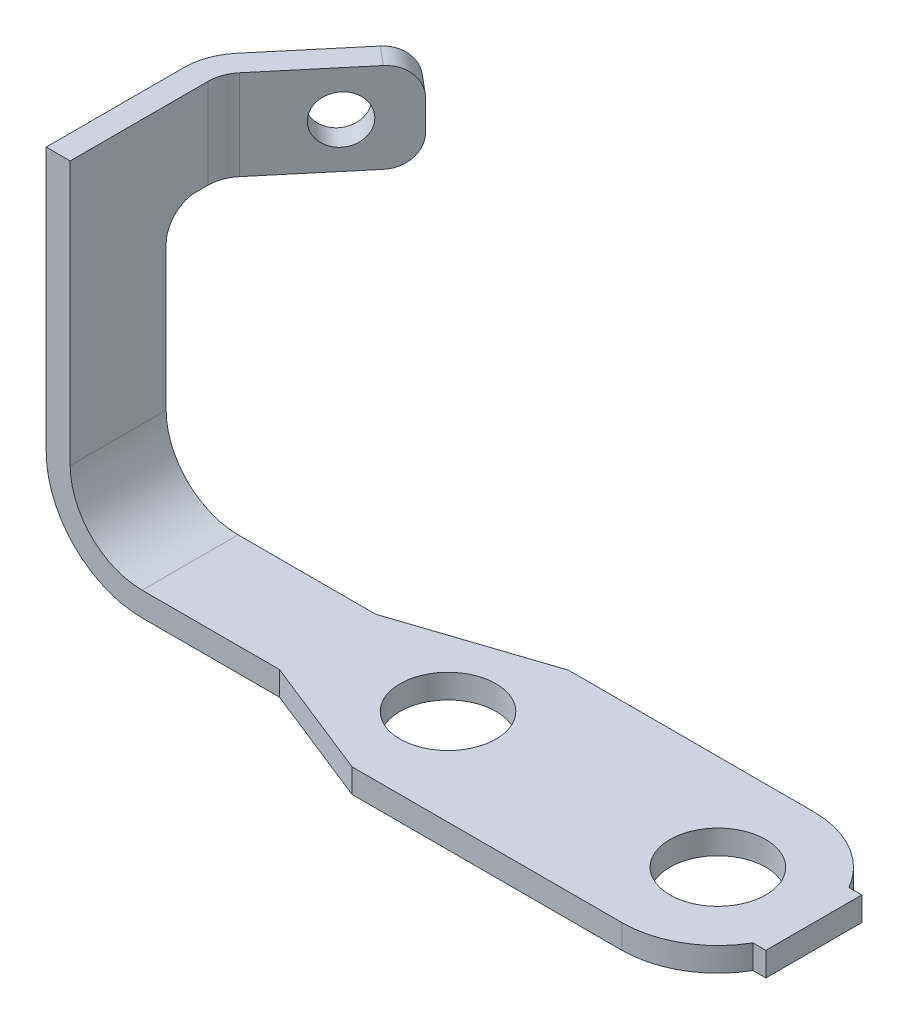
SolidWorks part; units mm, degrees
ref_plane "Front Plane" through (0, 0, 0) normal (0, 0, 1) x (1, 0, 0)
ref_plane "Top Plane" through (0, 0, 0) normal (0, 1, 0) x (1, 0, 0)
ref_plane "Right Plane" through (0, 0, 0) normal (1, 0, 0) x (0, 0, -1)
sketch "Sketch1" plane through (0, 0, 0) normal (0, 0, 1) x (1, 0, 0)
  line L0 (0, 0) -> (-104, 0)
  line L1 (-120, 16) -> (-120, 60)
  arc A0 (-104, 0) -> (-120, 16) centre (-104, 16) cw
  point P5 (0, 0)
  point P7 (0, 0)
  point P8 (0, 0)
  dimension "D3" = 16
  dimension "D1" = 120
  dimension "D2" = 60
extrude "Extrude-Thin1" add sketch "Sketch1" along normal mid plane 16 thin thin type one direction wall 4
sketch "Sketch3" plane through (0, 4, 0) normal (0, 1, 0) x (1, 0, 0)
  line L0 (-16, 16) -> (-56.9066, 16)
  line L1 (-56.9066, 16) -> (-81.1003, 8)
  line L2 (0, 8) -> (-104, 8) construction
  line L3 (-81.1003, -8) -> (-81.1003, 8)
  line L4 (0, -8) -> (-104, -8) construction
  line L5 (-81.1003, -8) -> (-61, -16)
  line L6 (-61, -16) -> (-16, -16)
  circle A0 centre (-16, 0) radius 16
  circle A1 centre (-16, 0) radius 8
  circle A2 centre (-61, 0) radius 8
  line M3 (0, 8) -> (-104, 8)
  line M5 (-104, -8) -> (0, -8)
  dimension "D1" = 32
  dimension "D2" = 16
  dimension "D3" = 45
  dimension "D4" = 40
extrude "Boss-Extrude4" add sketch "Sketch3" against normal blind 4 contours A0 L0 L1 M3 | A0 M3 | A0 M5 | A0 L5 L6 M5 | A2 A0 M5 M3 region at (-47.8631, 4, -11.7902) region at (-16, 4, -11.2803) region at (-43.0709, 4, 0) region at (-16, 4, 11.2803) region at (-48.6992, 4, 11.8601)
extrude "Cut-Extrude1" cut sketch "Sketch3<3>" against normal blind 4 contours A2 | A1 region at (-16, 4, 0) region at (-61, 4, 0)
sketch "Sketch3<3>" plane through (0, 4, 0) normal (0, 1, 0) x (1, 0, 0) same geometry as "Sketch3"
sketch "Sketch4" plane through (0, 60, 0) normal (0, 1, 0) x (1, 0, 0)
  line L0 (-120, 8) -> (-120, 15)
  line L1 (-117.6604, 21.4279) -> (-103.5191, 38.2809)
  line L2 (-104, 8) -> (-116, 8) construction
  arc A0 (-120, 15) -> (-117.6604, 21.4279) centre (-110, 15) cw
  dimension "D1" = 10
  dimension "D2" = 7
  dimension "D3" = 22
  dimension "D4" = 50
extrude "Extrude-Thin2" add sketch "Sketch4" against normal blind 15 thin thin type one direction wall 4
fillet "Fillet1" radius 5 1 edges at (-118, 45, -8)
fillet "Fillet2" radius 5 2 edges at (-101.987, 45, -36.9953) (-101.987, 60, -36.9953)
sketch "Sketch5" plane through (-76.533, 0, -64.2188) normal (0.766, 0, 0.6428) x (0.6428, 0, -0.766)
  line L0 (-37.216, 50) -> (-37.216, 55) construction
  circle A0 centre (-47.216, 52.5) radius 4
  point P4 (0, 0)
  point P5 (-37.216, 52.5)
  point P6 (0, 0)
  dimension "D1" = 8
  dimension "D2" = 10
extrude "Cut-Extrude2" cut sketch "Sketch5" against normal blind 15
